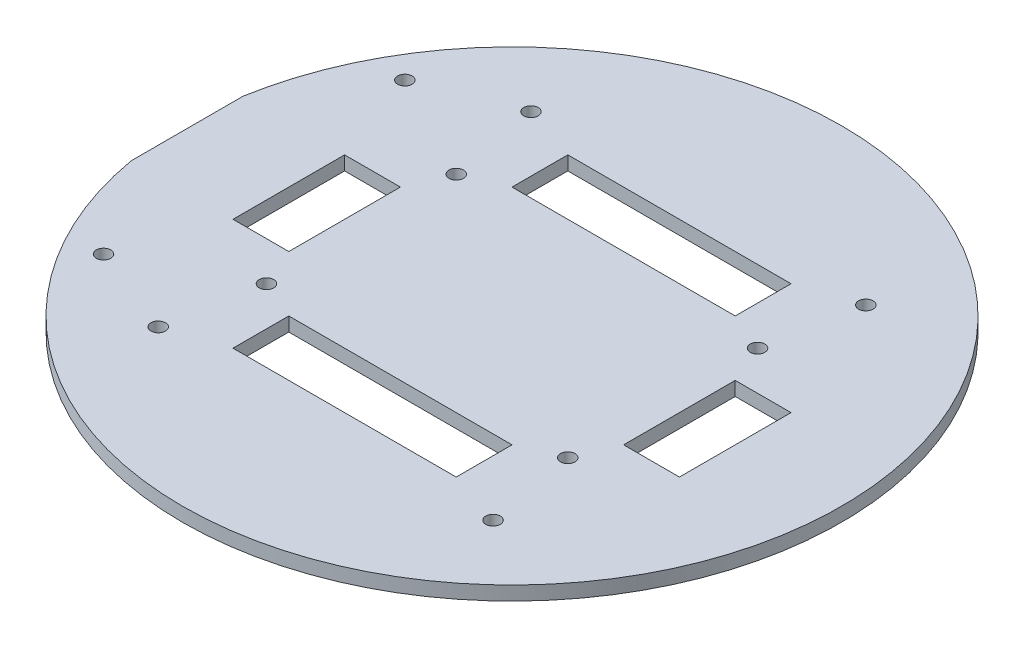
SolidWorks part; units mm, degrees
material "Acrylic (Medium-high impact)"
ref_plane "Front Plane" through (0, 0, 0) normal (0, 0, 1) x (1, 0, 0)
ref_plane "Top Plane" through (0, 0, 0) normal (0, 1, 0) x (1, 0, 0)
ref_plane "Right Plane" through (0, 0, 0) normal (1, 0, 0) x (0, 0, -1)
sketch "Sketch1" plane through (0, 0, 0) normal (0, 1, 0) x (1, 0, 0)
  line L0 (-73.9169, 12.7) -> (-73.9169, -12.7)
  line L1 (-73.9169, 12.7) -> (-73.9169, -12.7) construction
  line L2 (-34.29, 21.59) -> (34.29, 21.59) construction
  line L3 (34.29, 21.59) -> (34.29, -21.59) construction
  line L4 (34.29, -21.59) -> (-34.29, -21.59) construction
  line L5 (-34.29, -21.59) -> (-34.29, 21.59) construction
  line L6 (0, 21.59) -> (0, 75) construction
  line L7 (34.29, 0) -> (75, 0) construction
  line L8 (0, -25.4) -> (0, -21.59) construction
  line L9 (-34.29, 0) -> (-38.1, 0) construction
  line L10 (-25.4, 38.1) -> (25.4, 38.1)
  line L11 (-25.4, 38.1) -> (-25.4, 25.4)
  line L12 (-25.4, 25.4) -> (25.4, 25.4)
  line L13 (25.4, 38.1) -> (25.4, 25.4)
  line L14 (38.1, 12.7) -> (50.8, 12.7)
  line L15 (38.1, 12.7) -> (38.1, -12.7)
  line L16 (38.1, -12.7) -> (50.8, -12.7)
  line L17 (50.8, 12.7) -> (50.8, -12.7)
  line L18 (25.4, -25.4) -> (-25.4, -25.4)
  line L19 (25.4, -25.4) -> (25.4, -38.1)
  line L20 (25.4, -38.1) -> (-25.4, -38.1)
  line L21 (-25.4, -25.4) -> (-25.4, -38.1)
  line L22 (-50.8, -12.7) -> (-38.1, -12.7)
  line L23 (-50.8, -12.7) -> (-50.8, 12.7)
  line L24 (-50.8, 12.7) -> (-38.1, 12.7)
  line L25 (-38.1, -12.7) -> (-38.1, 12.7)
  line L26 (38.1, 12.7) -> (34.29, 12.7) construction
  line L27 (25.4, 25.4) -> (25.4, 21.59) construction
  arc A0 (-73.9169, -12.7) -> (-73.9169, 12.7) centre (0, 0) ccw
  arc A1 (55.356, -50.6035) -> (55.356, 50.6035) centre (0, 0) ccw construction
  circle A2 centre (-34.29, 21.59) radius 1.651
  circle A3 centre (34.29, 21.59) radius 1.651
  circle A4 centre (-34.29, -21.59) radius 1.651
  circle A5 centre (34.29, -21.59) radius 1.651
  circle A6 centre (-39.6269, 47.4285) radius 1.651 construction
  circle A7 centre (38.1, -42.418) radius 1.651
  circle A8 centre (-38.1, -42.418) radius 1.651
  circle A9 centre (-58.6769, -34.29) radius 1.651
  circle A10 centre (-58.6769, 34.29) radius 1.651
  circle A11 centre (-38.1, 42.418) radius 1.651
  circle A12 centre (38.1, 42.418) radius 1.651
  circle A13 centre (51.7494, -47.4285) radius 1.651 construction
  dimension "D1" = 68.58
  dimension "D2" = 43.18
  dimension "D3" = 3.81
  dimension "D4" = 12.7
  dimension "D5" = 50.8
  dimension "D6" = 25.4
extrude "Boss-Extrude1" add sketch "Sketch1" along normal blind 3.175
